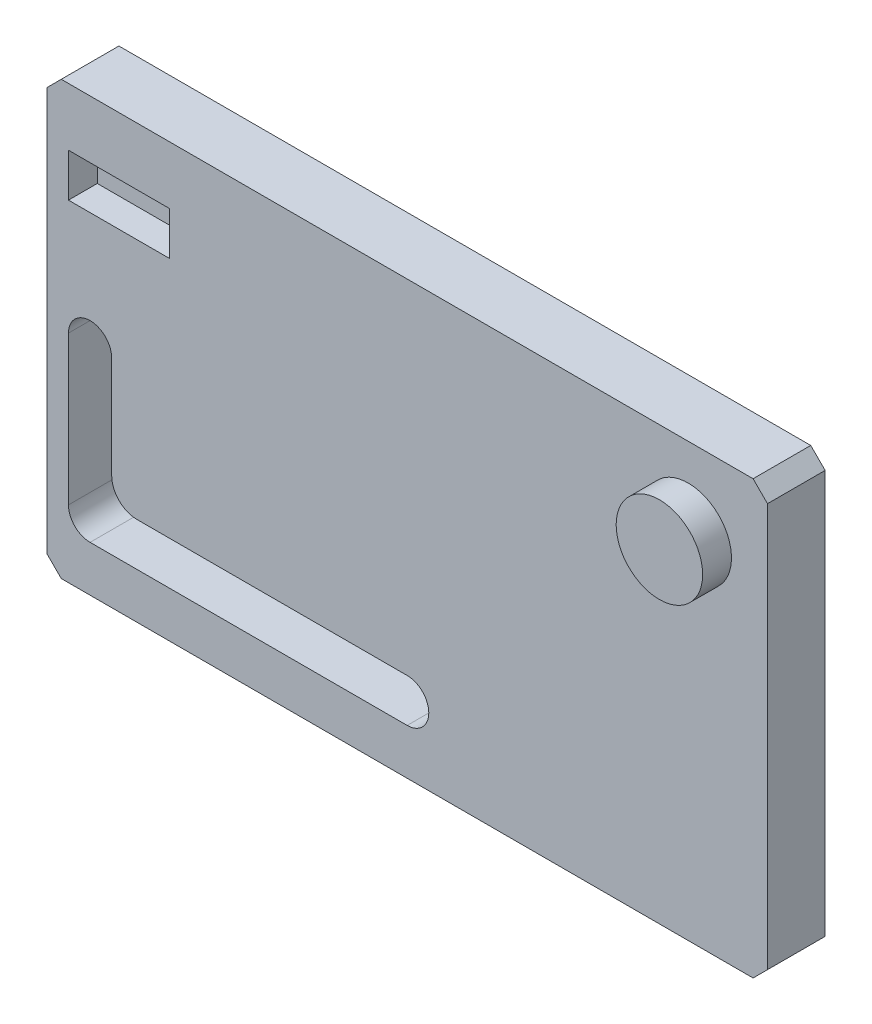
SolidWorks part; units mm, degrees
material "PMMA"
ref_plane "Front Plane" through (0, 0, 0) normal (0, 0, 1) x (1, 0, 0)
ref_plane "Top Plane" through (0, 0, 0) normal (0, 1, 0) x (1, 0, 0)
ref_plane "Right Plane" through (0, 0, 0) normal (1, 0, 0) x (0, 0, -1)
sketch "Sketch1" plane through (0, 0, 0) normal (0, 0, 1) x (1, 0, 0)
  line L5 (-12.5, -7.5) -> (12.5, -7.5)
  line L6 (-12.5, -7.5) -> (-12.5, 7.5)
  line L7 (-12.5, 7.5) -> (12.5, 7.5)
  line L8 (12.5, -7.5) -> (12.5, 7.5)
  line L9 (-12.5, -7.5) -> (12.5, 7.5) construction
  line L10 (-12.5, 7.5) -> (12.5, -7.5) construction
  point P0 (0, 0)
  dimension "D1" = 25
  dimension "D2" = 15
extrude "Boss-Extrude1" add sketch "Sketch1" along normal blind 2 contours L7 L8 L5 L6
chamfer "Chamfer1" distance 0.5 angle 45 4 edges at (-12.5, -7.5, 1) (12.5, -7.5, 1) (-12.5, 7.5, 1) (12.5, 7.5, 1)
sketch "Sketch2" plane through (0, 0, 2) normal (0, 0, 1) x (1, 0, 0)
  line L0 (12.5, -7) -> (12.5, 7) construction
  line L1 (-12, 7.5) -> (12, 7.5) construction
  circle A0 centre (9.75, 4.7447) radius 1.5
  dimension "D1" = 3
  dimension "D2" = 2.75
  dimension "D3" = 2.7553
extrude "Boss-Extrude2" add sketch "Sketch2" along normal blind 1
sketch "Sketch3" plane through (0, 0, 2) normal (0, 0, 1) x (1, 0, 0)
  line L0 (-12.5, -7) -> (-12.5, 7) construction
  line L1 (-11.75, 5.4947) -> (-8.25, 5.4947)
  line L2 (-11.75, 5.4947) -> (-11.75, 3.9947)
  line L3 (-11.75, 3.9947) -> (-8.25, 3.9947)
  line L4 (-8.25, 5.4947) -> (-8.25, 3.9947)
  line L5 (-11.75, 5.4947) -> (-8.25, 3.9947) construction
  line L6 (-11.75, 3.9947) -> (-8.25, 5.4947) construction
  point P0 (-10, 4.7447)
  dimension "D1" = 3.5
  dimension "D2" = 1.5
  dimension "D3" = 2.5
extrude "Cut-Extrude1" cut sketch "Sketch3" against normal offset from surface (1 mm away) 1 contours L1 L4 L3 L2 up to face at (0, 0, 0)
sketch "Sketch4" plane through (0, 0, 2) normal (0, 0, 1) x (1, 0, 0)
  line L0 (-11, -5.1616) -> (0, -5.1616) construction
  line L1 (-11, -4.4116) -> (0, -4.4116)
  line L2 (-11, -5.9116) -> (0, -5.9116)
  line L3 (-11, -5.1616) -> (-11, 0) construction
  line L4 (-11.75, -5.1616) -> (-11.75, 0)
  line L5 (-10.25, -5.1616) -> (-10.25, 0)
  arc A0 (-11, -4.4116) -> (-11, -5.9116) centre (-11, -5.1616) ccw
  arc A1 (0, -5.9116) -> (0, -4.4116) centre (0, -5.1616) ccw
  arc A3 (-11.75, -5.1616) -> (-10.25, -5.1616) centre (-11, -5.1616) ccw
  arc A4 (-10.25, 0) -> (-11.75, 0) centre (-11, 0) ccw
  point P2 (-5.5, -5.1616)
  point P7 (-11.75, -5.1616)
  point P14 (-11, -2.5808)
  point P19 (0, 0)
  dimension "D1" = 0.75
extrude "Cut-Extrude2" cut sketch "Sketch4" against normal up to next contours L1 A1 L2 A0
extrude "Cut-Extrude3" cut sketch "Sketch4<4>" against normal up to next contours L5 A4 L4 A3
sketch "Sketch4<4>" plane through (0, 0, 2) normal (0, 0, 1) x (1, 0, 0) same geometry as "Sketch4"
fillet "Fillet2" radius 0.875 1 edges at (-10.25, -4.4116, 1)
